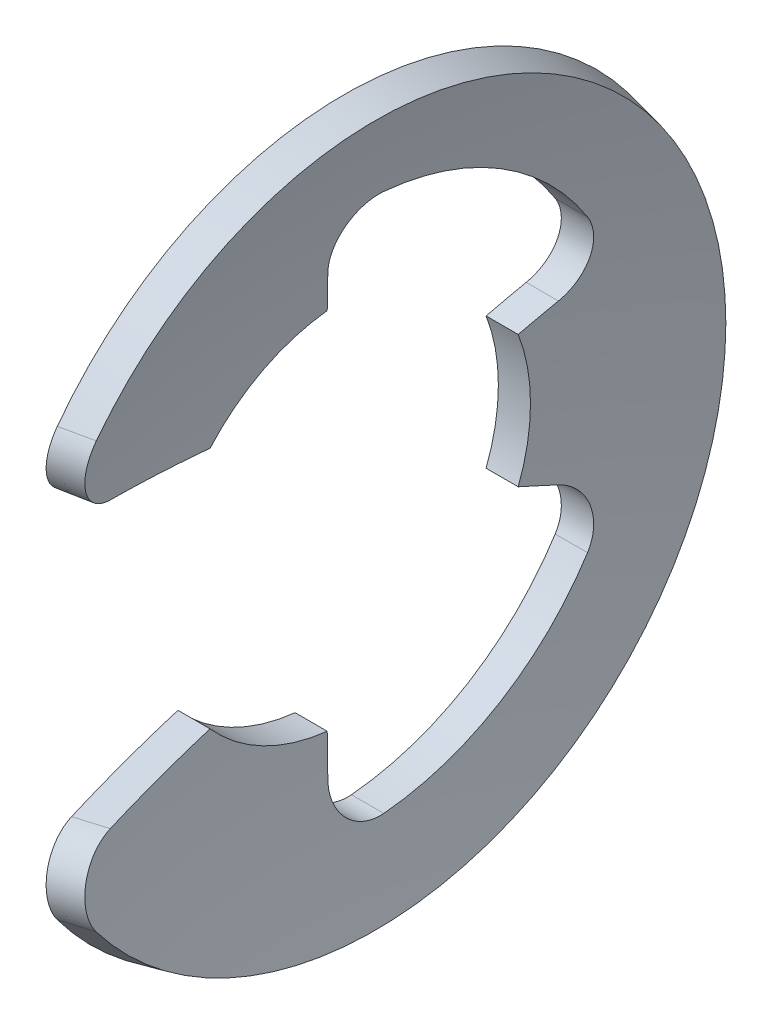
SolidWorks part; units mm, degrees
material "Cast Carbon Steel"
ref_plane "Front" through (0, 0, 0) normal (0, 0, 1) x (1, 0, 0)
ref_plane "Top" through (0, 0, 0) normal (0, 1, 0) x (1, 0, 0)
ref_plane "Right" through (0, 0, 0) normal (1, 0, 0) x (0, 0, -1)
sketch "Sketch2" plane through (0, 0, 0) normal (0, 1, 0) x (1, 0, 0)
  line L0 (0.284, 14.224) -> (1.524, 13.9498)
  line L1 (0, 0) -> (-1.27, 0)
  line L2 (1.524, 13.9498) -> (64.606, 0) construction
  line L3 (0, 0) -> (64.606, 0) construction
  arc A0 (0, 0) -> (1.524, 13.9498) centre (64.606, 0) cw
  arc A1 (-1.27, 0) -> (0.284, 14.224) centre (64.606, 0) cw
  dimension "Th" = 1.27
  dimension "Bh" = 2.794
  dimension "OD" = 28.448
revolve "Revolve1" add sketch "Sketch2" angle 360 about L3
ref_plane "Plane1" through (1.524, 0, 0) normal (1, 0, 0) x (0, 0, -1)
sketch "Sketch1" plane through (1.524, 0, 0) normal (1, 0, 0) x (0, 0, -1)
  line L0 (-12.8207, -6.1605) -> (-5.457, -4.8335)
  line L1 (-12.8207, 6.1605) -> (-5.457, 4.8335)
  line L2 (-0.7958, -7.2462) -> (-1.1743, -10.6926)
  line L3 (-0.7958, 7.2462) -> (-1.1743, 10.6926)
  line L4 (6.801, -2.6243) -> (10.0357, -3.8725)
  line L5 (6.801, 2.6243) -> (10.0357, 3.8725)
  line L6 (0, 0) -> (-14.224, 0) construction
  circle A0 centre (0, 0) radius 14.224 construction
  circle A1 centre (0, 0) radius 14.478 construction
  circle A2 centre (0, 0) radius 7.2898 construction
  arc A3 (-12.8207, -6.1605) -> (-12.8207, 6.1605) centre (0, 0) ccw construction
  arc A4 (-5.457, -4.8335) -> (-0.7958, -7.2462) centre (0, 0) ccw
  arc A5 (-5.457, 4.8335) -> (-0.7958, 7.2462) centre (0, 0) cw
  arc A6 (6.801, 2.6243) -> (6.801, -2.6243) centre (0, 0) cw
  arc A7 (-1.1743, -10.6926) -> (10.0357, -3.8725) centre (0, 0) ccw
  arc A8 (10.0357, 3.8725) -> (-1.1743, 10.6926) centre (0, 0) ccw
  arc A9 (-12.8207, -6.1605) -> (-12.8207, 6.1605) centre (0, 0) cw
  dimension "D1" = 10.7569
  dimension "L" = 28.956
  dimension "D" = 14.5796
  dimension "D2" = 13.1216
  dimension "D3" = 5.2487
  dimension "D4" = 5.2487
extrude "Cut-Extrude1" cut sketch "Sketch1" against normal through all
fillet "Fillet1" radius 1.778 6 edges at (0.258, 10.6926, 1.1743) (0.258, 3.8725, -10.0357) (0.258, -3.8725, -10.0357) (0.258, -10.6926, 1.1743)
sketch "Sketch3" plane through (0, 0, 0) normal (0, 1, 0) x (1, 0, 0)
  line L0 (0.889, 9.525) -> (0.889, 7.366)
  line L1 (0.889, 7.366) -> (-1.27, 7.366)
  line L2 (-1.27, 7.366) -> (-1.27, 9.525)
  line L3 (-1.27, 9.525) -> (-15.3035, 9.525)
  line L4 (6.2865, 0) -> (6.2865, 8.4455)
  line L5 (-15.3035, 9.525) -> (-15.3035, 0)
  line L6 (-15.3035, 0) -> (6.2865, 0)
  line L7 (0, 0) -> (64.606, 0) construction
  line L8 (6.2865, 0) -> (6.2865, 9.525) construction
  line L9 (6.2865, 9.525) -> (0.889, 9.525) construction
  line L10 (6.2865, 0) -> (17.2631, 0) construction
  line L11 (6.2865, 8.4455) -> (5.207, 9.525)
  line L12 (5.207, 9.525) -> (0.889, 9.525)
  point P2 (0.889, 8.4455)
  dimension "D1" = 5.3975
  dimension "Ds" = 19.05
  dimension "Dg" = 14.732
  dimension "W" = 2.159
  dimension "D2" = 21.59
  dimension "D3" = 45
revolve "Revolve2" [suppressed] add sketch "Sketch3" angle 360 about L3
ref_axis "Axis1" through (-0.9904, 0, 0) along (1, 0, 0)
equation "\"D2@Sketch3\" = \"W@Sketch3\"*10"
equation "\"D1@Sketch3\" = \"D2@Sketch3\"/4"
equation "\"D1@Sketch1\" = (\"OD@Sketch2\"+\"D@Sketch1\")/4"
equation "\"D2@Sketch1\" = \"D@Sketch1\"*.9"
equation "\"D4@Sketch1\" = \"D2@Sketch1\"/2.5"
equation "\"D3@Sketch1\" = \"D4@Sketch1\""
